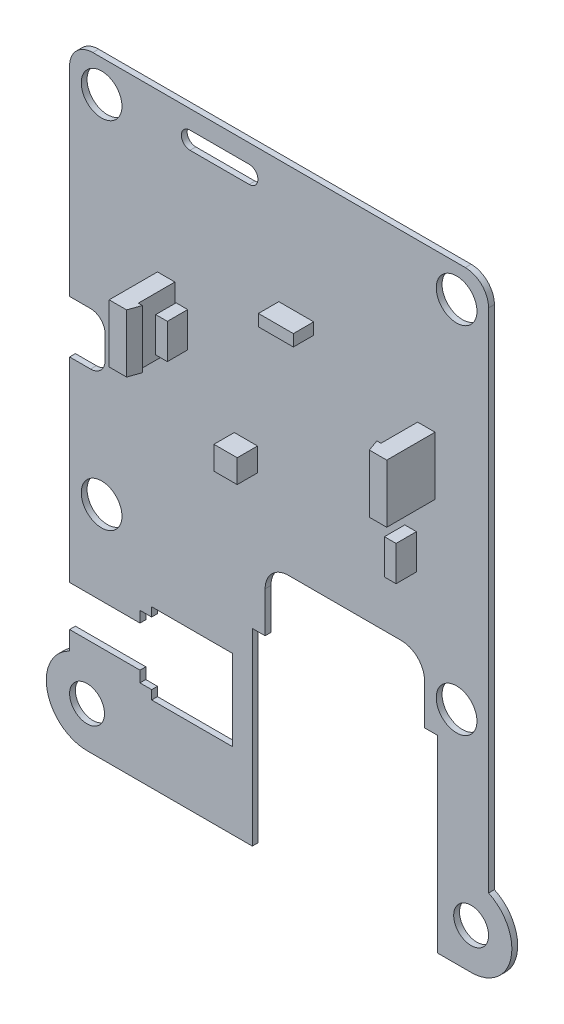
SolidWorks part; units mm, degrees
ref_plane "Front Plane" through (0, 0, 0) normal (0, 0, 1) x (1, 0, 0)
ref_plane "Top Plane" through (0, 0, 0) normal (0, 1, 0) x (1, 0, 0)
ref_plane "Right Plane" through (0, 0, 0) normal (1, 0, 0) x (0, 0, -1)
sketch "Sketch1" plane through (0, 0, 0) normal (0, 0, 1) x (1, 0, 0)
  line L9 (18, -18) -> (-18, -18)
  line L14 (16, 18) -> (-16, 18)
  line L15 (-18, 16) -> (-18, -1.15)
  line L16 (-18, -1.15) -> (-16.2, -1.15)
  line L17 (-14.95, -2.4) -> (-14.95, -4.4)
  line L18 (-16.2, -5.65) -> (-18, -5.65)
  line L19 (-18, -5.65) -> (-18, -18)
  line L20 (-18, -18) -> (-1.2, -18)
  line L21 (-1.2, -18) -> (-1.2, -14.5)
  line L22 (0.8, -12.5) -> (10.5, -12.5)
  line L23 (12.5, -14.5) -> (12.5, -18)
  line L24 (12.5, -18) -> (18, -18)
  line L25 (18, -18) -> (18, 16)
  line L26 (16, 18) -> (-16, 18)
  line L27 (-18, 16) -> (-18, -1.15)
  line L28 (-18, -1.15) -> (-16.2, -1.15)
  line L29 (-14.95, -2.4) -> (-14.95, -4.4)
  line L30 (-16.2, -5.65) -> (-18, -5.65)
  line L31 (-18, -5.65) -> (-18, -18)
  line L32 (-18, -18) -> (-1.2, -18)
  line L33 (-1.2, -18) -> (-1.2, -14.5)
  line L34 (0.8, -12.5) -> (10.5, -12.5)
  line L35 (12.5, -14.5) -> (12.5, -18)
  line L36 (12.5, -18) -> (18, -18)
  line L37 (18, -18) -> (18, 16)
  line L41 (13.6, -18) -> (13.6, -34.2)
  line L42 (13.6, -34.2) -> (16.5, -34.2)
  line L43 (18, -27.5377) -> (18, -18)
  line L44 (18, -18) -> (13.6, -18)
  line L46 (13.6, -18) -> (13.6, -34.2)
  line L47 (13.6, -34.2) -> (16.5, -34.2)
  line L48 (18, -27.5377) -> (18, -18)
  line L49 (18, -18) -> (13.6, -18)
  line L66 (-2.3, -18) -> (-18, -18)
  line L153 (-11.95, -22.43) -> (-11.95, -21.48)
  line L154 (-11.95, -21.48) -> (-10.95, -21.48)
  line L155 (-10.95, -21.48) -> (-10.95, -20.71)
  line L156 (-10.95, -20.71) -> (-4.01, -20.71)
  line L157 (-4.01, -20.71) -> (-4.01, -27.65)
  line L158 (-4.01, -27.65) -> (-10.95, -27.65)
  line L159 (-10.95, -27.65) -> (-10.95, -26.88)
  line L160 (-10.95, -26.88) -> (-11.95, -26.88)
  line L161 (-11.95, -26.88) -> (-11.95, -25.93)
  line L162 (-11.95, -25.93) -> (-18, -25.93)
  line L163 (-18, -25.93) -> (-18, -27.5377)
  line L164 (-16.5, -34.2) -> (-2.3, -34.2)
  line L165 (-2.3, -34.2) -> (-2.3, -18)
  line L166 (-2.3, -18) -> (-18, -18)
  line L167 (-18, -18) -> (-18, -22.43)
  line L168 (-18, -22.43) -> (-11.95, -22.43)
  line L169 (-11.95, -22.43) -> (-11.95, -21.48)
  line L170 (-11.95, -21.48) -> (-10.95, -21.48)
  line L171 (-10.95, -21.48) -> (-10.95, -20.71)
  line L172 (-10.95, -20.71) -> (-4.01, -20.71)
  line L173 (-4.01, -20.71) -> (-4.01, -27.65)
  line L174 (-4.01, -27.65) -> (-10.95, -27.65)
  line L175 (-10.95, -27.65) -> (-10.95, -26.88)
  line L176 (-10.95, -26.88) -> (-11.95, -26.88)
  line L177 (-11.95, -26.88) -> (-11.95, -25.93)
  line L178 (-11.95, -25.93) -> (-18, -25.93)
  line L179 (-18, -25.93) -> (-18, -27.5377)
  line L180 (-16.5, -34.2) -> (-2.3, -34.2)
  line L181 (-2.3, -34.2) -> (-2.3, -18)
  line L182 (-2.3, -18) -> (-18, -18)
  line L183 (-18, -18) -> (-18, -22.43)
  line L184 (-18, -22.43) -> (-11.95, -22.43)
  line L229 (-7.65, 14.9) -> (-2.57, 14.9) construction
  line L230 (-7.65, 16.4) -> (-2.57, 16.4) construction
  line L231 (-7.65, 16.4) -> (-2.57, 16.4)
  line L232 (-7.65, 14.9) -> (-2.57, 14.9)
  circle A2 centre (16.5, -30.7) radius 1.5 construction
  arc A3 (16.5, -34.2) -> (18, -27.5377) centre (16.5, -30.7) ccw
  circle A4 centre (15.25, -15.25) radius 1.75 construction
  circle A5 centre (15.25, 15.25) radius 1.75 construction
  circle A6 centre (-15.25, -15.25) radius 1.75 construction
  arc A7 (-16, 18) -> (-18, 16) centre (-16, 16) ccw
  arc A8 (-14.95, -2.4) -> (-16.2, -1.15) centre (-16.2, -2.4) ccw
  arc A9 (-16.2, -5.65) -> (-14.95, -4.4) centre (-16.2, -4.4) ccw
  arc A10 (0.8, -12.5) -> (-1.2, -14.5) centre (0.8, -14.5) ccw
  arc A11 (12.5, -14.5) -> (10.5, -12.5) centre (10.5, -14.5) ccw
  arc A12 (18, 16) -> (16, 18) centre (16, 16) ccw
  arc A14 (-16, 18) -> (-18, 16) centre (-16, 16) ccw
  arc A15 (-14.95, -2.4) -> (-16.2, -1.15) centre (-16.2, -2.4) ccw
  arc A16 (-16.2, -5.65) -> (-14.95, -4.4) centre (-16.2, -4.4) ccw
  arc A17 (0.8, -12.5) -> (-1.2, -14.5) centre (0.8, -14.5) ccw
  arc A19 (12.5, -14.5) -> (10.5, -12.5) centre (10.5, -14.5) ccw
  arc A20 (18, 16) -> (16, 18) centre (16, 16) ccw
  circle A21 centre (-15.25, 15.25) radius 1.75 construction
  arc A22 (16.5, -34.2) -> (18, -27.5377) centre (16.5, -30.7) ccw
  circle A23 centre (15.25, -15.25) radius 1.75
  circle A24 centre (15.25, 15.25) radius 1.75
  circle A25 centre (-15.25, -15.25) radius 1.75
  circle A26 centre (-15.25, 15.25) radius 1.75
  circle A36 centre (16.5, -30.7) radius 1.5
  circle A54 centre (-16.5, -30.7) radius 1.5 construction
  arc A55 (-18, -27.5377) -> (-16.5, -34.2) centre (-16.5, -30.7) ccw
  arc A56 (-18, -27.5377) -> (-16.5, -34.2) centre (-16.5, -30.7) ccw
  circle A57 centre (-16.5, -30.7) radius 1.5
  arc A62 (-2.57, 14.9) -> (-2.57, 16.4) centre (-2.57, 15.65) ccw construction
  arc A63 (-7.65, 16.4) -> (-7.65, 14.9) centre (-7.65, 15.65) ccw construction
  arc A64 (-7.65, 16.4) -> (-7.65, 14.9) centre (-7.65, 15.65) ccw
  arc A65 (-2.57, 14.9) -> (-2.57, 16.4) centre (-2.57, 15.65) ccw
  point P3 (16, -20.1266)
  point P5 (0, 0)
  point P12 (0, 0)
  point P15 (-2.3, -18)
  point P20 (0, 0)
  point P22 (0, 0)
  point P23 (0, 0)
  point P24 (0, 0)
  point P25 (0, 0)
  dimension "D1" = 0
  dimension "D2" = 0
  dimension "D3" = 0
extrude "Base shape" add sketch "Sketch1" along normal blind 0.5 contours L37 A20 L26 A14 L27 L28 A15 L29 A16 L30 L31 L32 L33 A17 L34 A19 L35 L36 A26 A25 A24 A23 | L36 | L32 | L47 A22 L48 L9 L46 A36 region at (16.1034, -26.208, 0) region at (-0.1312, 0.8573, 0) region at (-2.5399, -26.1, 0)
sketch "Sketch2" plane through (0, 0, 0.5) normal (0, 0, 1) x (1, 0, 0)
  line L0 (1.475, 16.95) -> (1.475, -13.05) construction
  line L1 (-7.85, 1.45) -> (-8.85, 1.45) construction
  line L2 (-0.025, 7.45) -> (2.975, 7.45)
  line L3 (-0.025, 7.45) -> (-0.025, 6.45)
  line L4 (11.8, 16.95) -> (-8.85, 16.95)
  line L5 (-8.85, 16.95) -> (-8.85, -13.05)
  line L6 (-8.85, -13.05) -> (11.8, -13.05)
  line L7 (11.8, -13.05) -> (11.8, 16.95)
  line L8 (11.8, 16.95) -> (-8.85, 16.95)
  line L9 (-8.85, 16.95) -> (-8.85, -13.05)
  line L10 (-8.85, -13.05) -> (11.8, -13.05)
  line L11 (11.8, -13.05) -> (11.8, 16.95)
  line L12 (-0.025, 6.45) -> (2.975, 6.45)
  line L13 (2.975, 7.45) -> (2.975, 6.45)
  line L14 (-0.025, 7.45) -> (2.975, 6.45) construction
  line L15 (-0.025, 6.45) -> (2.975, 7.45) construction
  line L16 (-8.85, 2.95) -> (-7.85, 2.95)
  line L17 (-8.85, 2.95) -> (-8.85, -0.05)
  line L18 (-8.85, -0.05) -> (-7.85, -0.05)
  line L19 (-7.85, 2.95) -> (-7.85, -0.05)
  line L20 (-3.85, -4.2) -> (-1.85, -4.2)
  line L21 (-3.85, -4.2) -> (-3.85, -6.2)
  line L22 (-3.85, -6.2) -> (-1.85, -6.2)
  line L23 (-1.85, -4.2) -> (-1.85, -6.2)
  line L24 (11.8, -3.75) -> (10.8, -3.75)
  line L25 (11.8, -3.75) -> (11.8, -6.75)
  line L26 (11.8, -6.75) -> (10.8, -6.75)
  line L27 (10.8, -3.75) -> (10.8, -6.75)
  line L28 (11.8, 1.95) -> (10.8, 1.95)
  line L29 (11.8, 1.95) -> (11.8, -1.05)
  line L30 (11.8, -1.05) -> (10.8, -1.05)
  line L31 (10.8, 1.95) -> (10.8, -1.05)
  line L32 (-3.85, -5.2) -> (-1.85, -5.2) construction
  line L33 (-2.85, -4.2) -> (-2.85, -6.2) construction
  line L34 (10.8, 0.45) -> (11.8, 0.45) construction
  line L35 (10.8, -5.25) -> (11.8, -5.25) construction
  point P6 (1.475, 6.95)
  dimension "D2" = 3
  dimension "D3" = 1
  dimension "D4" = 10
  dimension "D5" = 7.8
  dimension "D6" = 16.5
  dimension "D7" = 7.85
  dimension "D8" = 6
  dimension "D9" = 2
  dimension "D10" = 15.5
  dimension "D1" = 0
extrude "RX supports" add sketch "Sketch2" along normal blind 1.75 contours L13 L2 L3 L12 | L19 L16 L9 L18 | L23 L20 L21 L22 | L28 L31 L30 L11 | L24 L27 L26 L11 region at (1.475, 6.95, 0.5) region at (11.3, 0.45, 0.5) region at (-8.35, 1.45, 0.5) region at (11.3, -5.25, 0.5) region at (-2.85, -5.2, 0.5)
sketch "Sketch3" plane through (0, 0, 0.5) normal (0, 0, 1) x (1, 0, 0)
  line L0 (-8.85, 1.95) -> (11.8, 1.95) construction
  line L1 (1.475, 16.95) -> (1.475, -13.05) construction
  line L2 (-8.95, 4.45) -> (-10.45, 4.45)
  line L3 (-8.95, 4.45) -> (-8.95, -0.55)
  line L4 (11.8, 16.95) -> (-8.85, 16.95)
  line L5 (-8.85, 16.95) -> (-8.85, -13.05)
  line L6 (-8.85, -13.05) -> (11.8, -13.05)
  line L7 (11.8, -13.05) -> (11.8, 16.95)
  line L8 (11.8, 16.95) -> (-8.85, 16.95)
  line L9 (-8.85, 16.95) -> (-8.85, -13.05)
  line L10 (-8.85, -13.05) -> (11.8, -13.05)
  line L11 (11.8, -13.05) -> (11.8, 16.95)
  line L12 (-8.95, -0.55) -> (-10.45, -0.55)
  line L13 (-10.45, 4.45) -> (-10.45, -0.55)
  line L14 (11.9, -0.55) -> (13.4, -0.55)
  line L15 (13.4, 4.45) -> (13.4, -0.55)
  line L16 (11.9, 4.45) -> (13.4, 4.45)
  line L17 (11.9, 4.45) -> (11.9, -0.55)
  point P10 (-10.45, 1.95)
  dimension "D2" = 5
  dimension "D3" = 1.5
  dimension "D4" = 0.1
  dimension "D1" = 0
extrude "Clip base" add sketch "Sketch3" along normal offset from surface (3.15 mm away) 0.2 contours L2 L13 L12 L3 | L16 L17 L14 L15 region at (-9.7, 1.95, 0.5) region at (12.65, 1.95, 0.5) offset beyond the face yes
sketch "Sketch4" plane through (0, 0, 3.65) normal (0, 0, 1) x (1, 0, 0)
  line L0 (-8.95, -0.55) -> (-10.45, -0.55) construction
  line L1 (-10.45, 4.45) -> (-8.6, 4.45)
  line L2 (-10.45, 4.45) -> (-10.45, -0.55)
  line L3 (-10.45, -0.55) -> (-8.6, -0.55)
  line L4 (-8.6, 4.45) -> (-8.6, -0.55)
  line L5 (-8.95, 4.45) -> (-8.95, -0.55) construction
  line L6 (-10.45, 1.95) -> (13.4, 1.95) construction
  line L7 (13.4, 4.45) -> (13.4, -0.55) construction
  line L8 (1.475, 4.45) -> (1.475, -0.55) construction
  line L9 (11.55, 4.45) -> (11.55, -0.55)
  line L10 (13.4, 4.45) -> (11.55, 4.45)
  line L11 (13.4, 4.45) -> (13.4, -0.55)
  line L12 (13.4, -0.55) -> (11.55, -0.55)
  point P17 (1.475, 1.95)
  dimension "D1" = 0.35
extrude "Clip top" add sketch "Sketch4" along normal blind 1
sketch "Sketch5" plane through (0, -0.55, 0) normal (0, -1, 0) x (1, 0, 0)
  line L0 (-8.6, 3.65) -> (-8.95, 4.65)
  line L1 (-10.45, 4.65) -> (-8.6, 4.65) construction
  line L2 (-8.95, 4.65) -> (-8.6, 4.65)
  line L3 (-8.6, 4.65) -> (-8.6, 3.65)
  line L4 (-8.95, 3.65) -> (-8.95, 0.5) construction
  line L5 (11.55, 3.65) -> (11.9, 4.65)
  line L6 (11.55, 4.65) -> (13.4, 4.65) construction
  line L7 (11.9, 4.65) -> (11.55, 4.65)
  line L8 (11.55, 4.65) -> (11.55, 3.65)
  line L9 (11.9, 3.65) -> (11.9, 0.5) construction
extrude "Clip chamfer" cut sketch "Sketch5" against normal up to next
